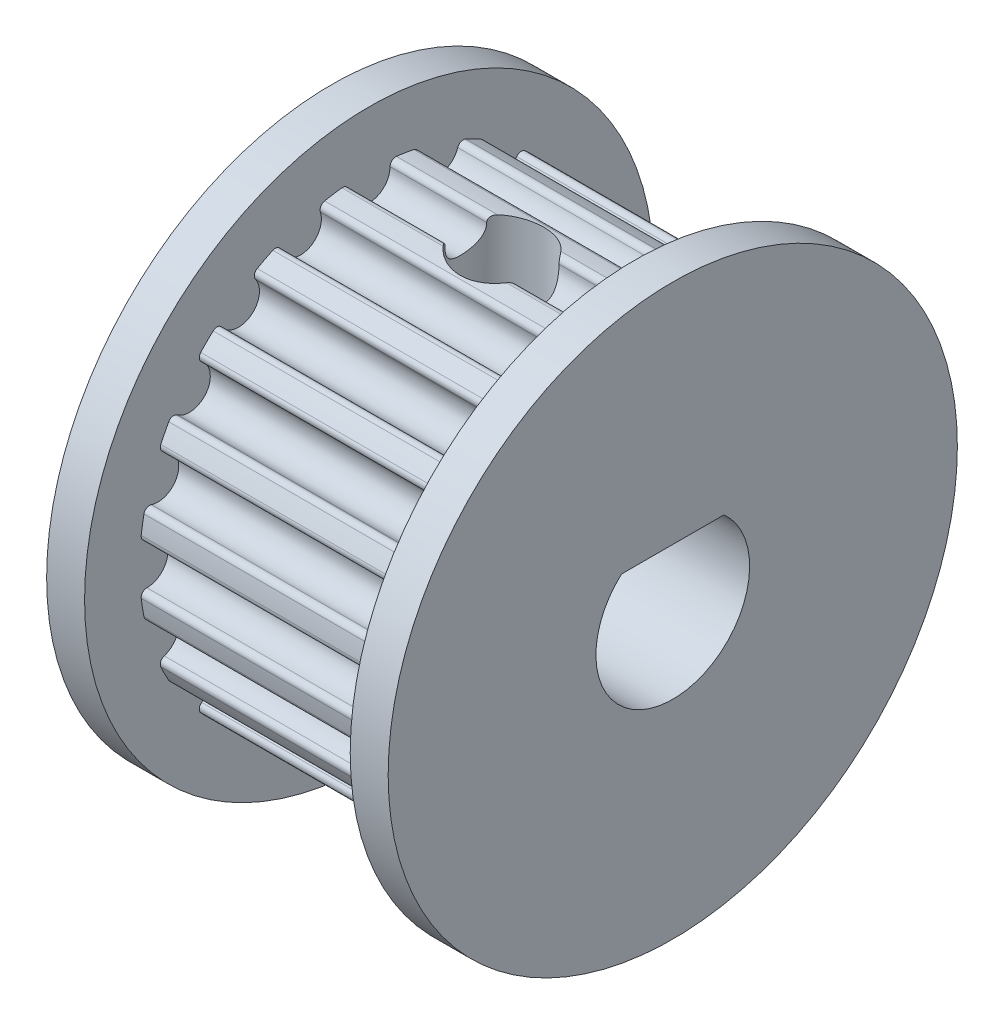
SolidWorks part; units mm, degrees
material "PLA Black"
ref_plane "Сверху" through (0, 0, 0) normal (0, 0, 1) x (1, 0, 0)
ref_plane "Справа" through (0, 0, 0) normal (0, 1, 0) x (1, 0, 0)
ref_plane "Спереди" through (0, 0, 0) normal (1, 0, 0) x (0, 0, -1)
sketch "Эскиз1" plane through (0, 0, 0) normal (0, 0, 1) x (1, 0, 0)
  line L0 (0, 7.5) -> (0, 0)
  line L3 (0, 7.5) -> (1, 7.5)
  line L4 (1, 6.05) -> (8, 6.05)
  line L5 (8, 6.05) -> (8, 7.5)
  line L7 (9, 0) -> (9, 7.5)
  line L11 (0, 0) -> (9, 0)
  line L12 (1, 7.5) -> (1, 6.05)
  line L13 (8, 7.5) -> (9, 7.5)
  dimension "D1" = 7.5
  dimension "D2" = 1
  dimension "D6" = 6.05
  dimension "D8" = 7
revolve "Body" add sketch "Эскиз1" angle 360 about L11 region at (4.5, 3.2146, 0)
sketch "Эскиз3" plane through (1, 0, 0) normal (1, 0, 0) x (0, 0, -1)
  line L0 (0, 0) -> (9.7637, 0) construction
  circle A0 centre (5.5684, -1.8093) radius 0.55
  circle A2 centre (4.7368, -3.4415) radius 0.55
  circle A3 centre (3.4415, -4.7368) radius 0.55
  circle A4 centre (1.8093, -5.5684) radius 0.55
  circle A5 centre (0, -5.855) radius 0.55
  circle A6 centre (5.855, 0) radius 0.55
  circle A7 centre (-1.8093, -5.5684) radius 0.55
  circle A8 centre (-3.4415, -4.7368) radius 0.55
  circle A9 centre (-4.7368, -3.4415) radius 0.55
  circle A10 centre (-5.5684, -1.8093) radius 0.55
  circle A11 centre (-5.855, 0) radius 0.55
  circle A12 centre (-5.5684, 1.8093) radius 0.55
  circle A13 centre (-4.7368, 3.4415) radius 0.55
  circle A14 centre (-3.4415, 4.7368) radius 0.55
  circle A17 centre (-1.8093, 5.5684) radius 0.55
  circle A18 centre (0, 5.855) radius 0.55
  circle A19 centre (1.8093, 5.5684) radius 0.55
  circle A20 centre (3.4415, 4.7368) radius 0.55
  circle A21 centre (4.7368, 3.4415) radius 0.55
  circle A22 centre (5.5684, 1.8093) radius 0.55
  point P45 (0, 0)
  dimension "D1" = 5.855
  dimension "D2" = 20
  dimension "D3" = 1.1
extrude "20tooth" cut sketch "Эскиз3" along normal blind 7
fillet "Скругление1" radius 0.15 40 edges at (4.5, -0.5223, -6.0274) (4.5, 0.5223, -6.0274) (4.5, -1.3659, -5.8938) (4.5, -2.3593, -5.571) (4.5, -3.1203, -5.1833) (4.5, -3.9654, -4.5693) (4.5, -4.5693, -3.9654) (4.5, -5.1833, -3.1203) (4.5, -5.571, -2.3593) (4.5, -5.8938, -1.3659) (4.5, -6.0274, -0.5223) (4.5, -6.0274, 0.5223) (4.5, -5.8938, 1.3659) (4.5, -5.571, 2.3593) (4.5, -5.1833, 3.1203) (4.5, -4.5693, 3.9654) (4.5, -3.9654, 4.5693) (4.5, -3.1203, 5.1833) (4.5, -2.3593, 5.571) (4.5, -1.3659, 5.8938) (4.5, -0.5223, 6.0274) (4.5, 0.5223, 6.0274) (4.5, 1.3659, 5.8938) (4.5, 2.3593, 5.571) (4.5, 3.1203, 5.1833) (4.5, 3.9654, 4.5693) (4.5, 4.5693, 3.9654) (4.5, 5.1833, 3.1203) (4.5, 5.571, 2.3593) (4.5, 5.8938, 1.3659) (4.5, 6.0274, -0.5223) (4.5, 5.571, -2.3593) (4.5, 4.5693, -3.9654) (4.5, 3.1203, -5.1833) (4.5, 1.3659, -5.8938) (4.5, 2.3593, -5.571) (4.5, 3.9654, -4.5693) (4.5, 6.0274, 0.5223) (4.5, 5.8938, -1.3659) (4.5, 5.1833, -3.1203)
sketch "Sketch1" plane through (9, 0, 0) normal (1, 0, 0) x (0, 0, -1)
  line L0 (-1.35, 1.5093) -> (1.35, 1.5093)
  arc A0 (-1.35, 1.5093) -> (1.35, 1.5093) centre (0, 0) ccw
  dimension "D1" = 4.05
  dimension "D2" = 2.7
extrude "Cut-Extrude1" cut sketch "Sketch1" against normal through all
hole_wizard "M2 Clearance Hole1" positions "Sketch3" profile "Sketch2" hole size "M2" standard "DIN" end condition through all
sketch "Sketch3" plane through (0, 1.5093, 0) normal (0, -1, 0) x (-1, 0, 0)
  line L0 (0, 0) -> (-9, 0) construction
  line L3 (0, 1.35) -> (0, -1.35) construction
  line L4 (-9, 1.35) -> (-9, -1.35) construction
  point P0 (-4.5, 0)
sketch "Sketch2" plane through (4.5, 1.5093, 0) normal (1, 0, 0) x (0, 0, -1)
  line L0 (0, 0) -> (0, 5.9907)
  line L1 (0, 5.9907) -> (1.1, 5.9907)
  line L2 (1.1, 5.9907) -> (1.1, 0)
  line L5 (1.1, 0) -> (0, 0)
  line L11 (0, -6.35) -> (0, 107.95) construction
  dimension "Thru Hole Dia." = 2.2
  dimension "Thru Hole Depth" = 5.9907
